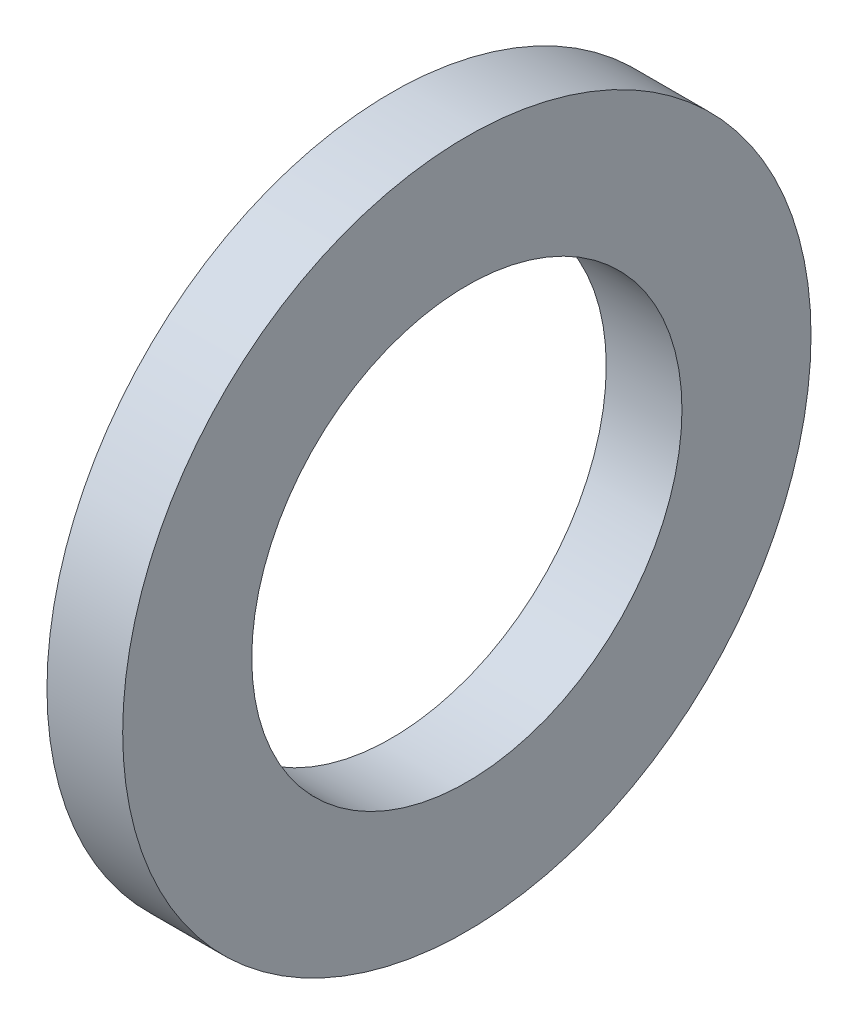
SolidWorks part; units mm, degrees
material "PTFE (general)"
ref_plane "Front Plane" through (0, 0, 0) normal (0, 0, 1) x (1, 0, 0)
ref_plane "Top Plane" through (0, 0, 0) normal (0, 1, 0) x (1, 0, 0)
ref_plane "Right Plane" through (0, 0, 0) normal (1, 0, 0) x (0, 0, -1)
sketch "Sketch1" plane through (0, 0, 0) normal (1, 0, 0) x (0, 0, -1)
  circle A0 centre (0, 0) radius 3.9688
  circle A1 centre (0, 0) radius 6.35
  dimension "D1" = 7.9375
  dimension "D2" = 12.7
extrude "Boss-Extrude1" add sketch "Sketch1" along normal blind 1.397
